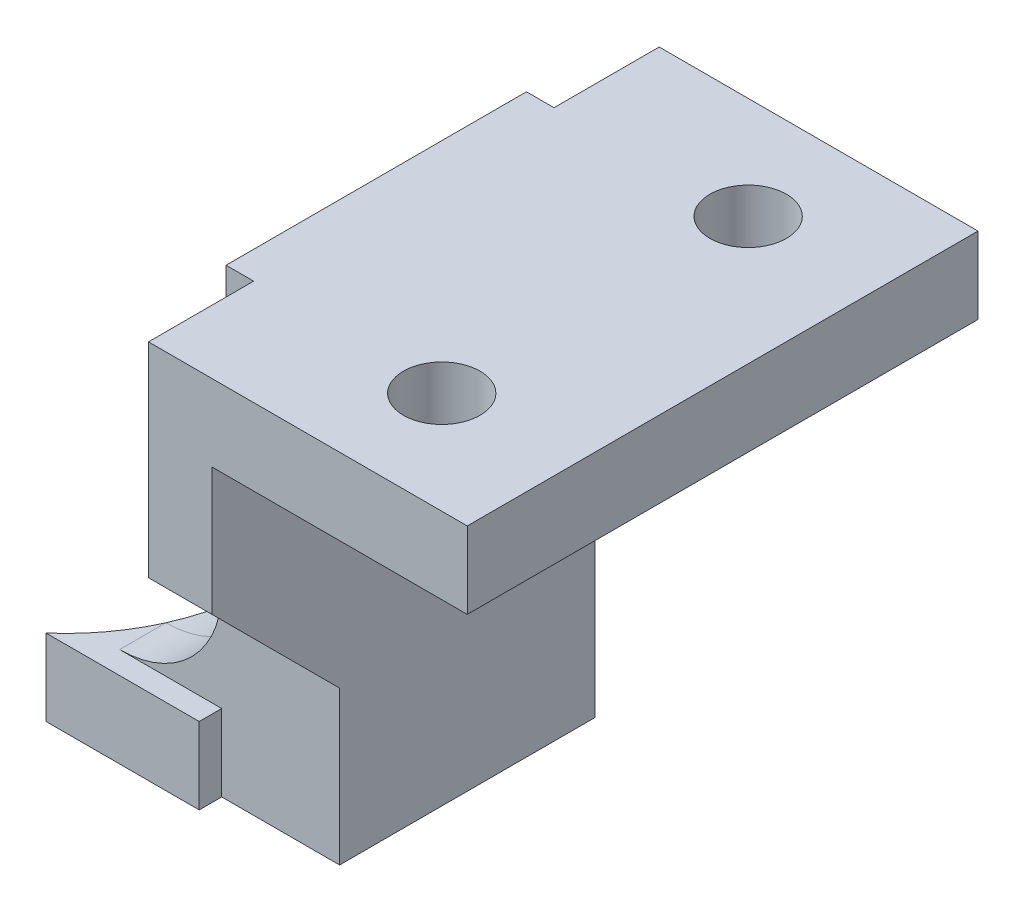
SolidWorks part; units mm, degrees
ref_plane "Front Plane" through (0, 0, 0) normal (0, 0, 1) x (1, 0, 0)
ref_plane "Top Plane" through (0, 0, 0) normal (0, 1, 0) x (1, 0, 0)
ref_plane "Right Plane" through (0, 0, 0) normal (1, 0, 0) x (0, 0, -1)
sketch "Sketch1" plane through (0, 0, 0) normal (0, 1, 0) x (1, 0, 0)
  line L0 (0, 8.5) -> (0, -8.5) construction
  line L1 (-3, -11.3279) -> (3, -11.3279)
  line L2 (-3, -11.3279) -> (-3, 11.3279)
  line L3 (-3, 11.3279) -> (3, 11.3279)
  line L4 (3, -11.3279) -> (3, -5)
  line L5 (-3, -11.3279) -> (3, 11.3279) construction
  line L6 (-3, 11.3279) -> (3, -11.3279) construction
  line L7 (3, -5) -> (7.6154, -5)
  line L8 (7.6154, -5) -> (7.6154, 5)
  line L9 (7.6154, 5) -> (3, 5)
  line L10 (3, 5) -> (3, 11.3279)
  circle A0 centre (0, 8.5) radius 1.5
  circle A1 centre (0, -8.5) radius 1.5
  point P0 (0, 0)
  point P10 (0, 0)
  point P13 (7.6154, 0)
  point P16 (-3, 0)
  dimension "D1" = 3
  dimension "D2" = 17
  dimension "D3" = 6
  dimension "D4" = 10
extrude "Boss-Extrude1" add sketch "Sketch1" along normal blind 3
sketch "Sketch3" plane through (0, 3, 0) normal (0, 1, 0) x (1, 0, 0)
  line L0 (7.6154, 5) -> (3, 5) construction
  line L1 (7.6154, 5) -> (3, 5)
  line L2 (7.6154, 5) -> (7.6154, -5)
  line L3 (7.6154, -5) -> (3, -5)
  line L4 (3, 5) -> (3, -5)
  line L5 (7.6154, -5) -> (7.6154, 5) construction
  line L6 (3, -5) -> (7.6154, -5) construction
extrude "Boss-Extrude2" add sketch "Sketch3" along normal blind 12.9998
fillet "Fillet7" radius 1 2 edges at (3, 1.5, -11.3279) (3, 1.5, 11.3279)
sketch "Sketch7" plane through (0, 0, 0) normal (0, -1, 0) x (1, 0, 0)
  line L0 (-3.6553, -6.3921) -> (-3.7819, 6.4785)
  arc A0 (-3.6553, -6.3921) -> (-3.7819, 6.4785) centre (-8.1114, 0) ccw
extrude "Cut-Extrude4" cut sketch "Sketch7" against normal blind 10
sketch "Sketch9" plane through (0, 15.9998, 0) normal (0, 1, 0) x (1, 0, 0)
  line L1 (4.0509, -10) -> (17.6154, -10)
  line L2 (4.0509, -10) -> (4.0509, 10)
  line L3 (4.0509, 10) -> (17.6154, 10)
  line L4 (17.6154, -10) -> (17.6154, 10)
  line L6 (7.6154, -5) -> (7.6154, 5) construction
  line L7 (7.6154, -5) -> (17.6154, -5) construction
  line L8 (12.6154, -6) -> (12.6154, 6) construction
  circle A0 centre (12.6154, 6) radius 1.5
  circle A1 centre (12.6154, -6) radius 1.5
  point P7 (7.6154, 0)
  point P8 (4.0509, 0)
  point P16 (12.6154, -5)
  point P18 (12.6154, 0)
  dimension "D3" = 3
  dimension "D1" = 20
  dimension "D2" = 10
  dimension "D4" = 12
extrude "Boss-Extrude3" add sketch "Sketch9" along normal blind 3
chamfer "Chamfer1" distance 10 angle 45 1 edges at (5.8332, 15.9998, 5)
chamfer "Chamfer2" distance 10 angle 45 1 edges at (5.8332, 15.9998, -5)
fillet "Fillet8" radius 4 1 edges at (3, 3, 0)
sketch "Sketch10" plane through (0, 3, 0) normal (0, 1, 0) x (1, 0, 0)
  line L1 (-3, 5.8812) -> (5.1312, 5.8812)
  line L2 (-3, 5.8812) -> (-3, 12.6309)
  line L3 (-3, 12.6309) -> (5.1312, 12.6309)
  line L4 (5.1312, 5.8812) -> (5.1312, 12.6309)
  line L5 (-3, -5.8812) -> (5.1312, -5.8812)
  line L6 (-3, -5.8812) -> (-3, -12.8947)
  line L7 (-3, -12.8947) -> (5.1312, -12.8947)
  line L8 (5.1312, -5.8812) -> (5.1312, -12.8947)
extrude "Cut-Extrude5" cut sketch "Sketch10" against normal through all both and the other way through all
